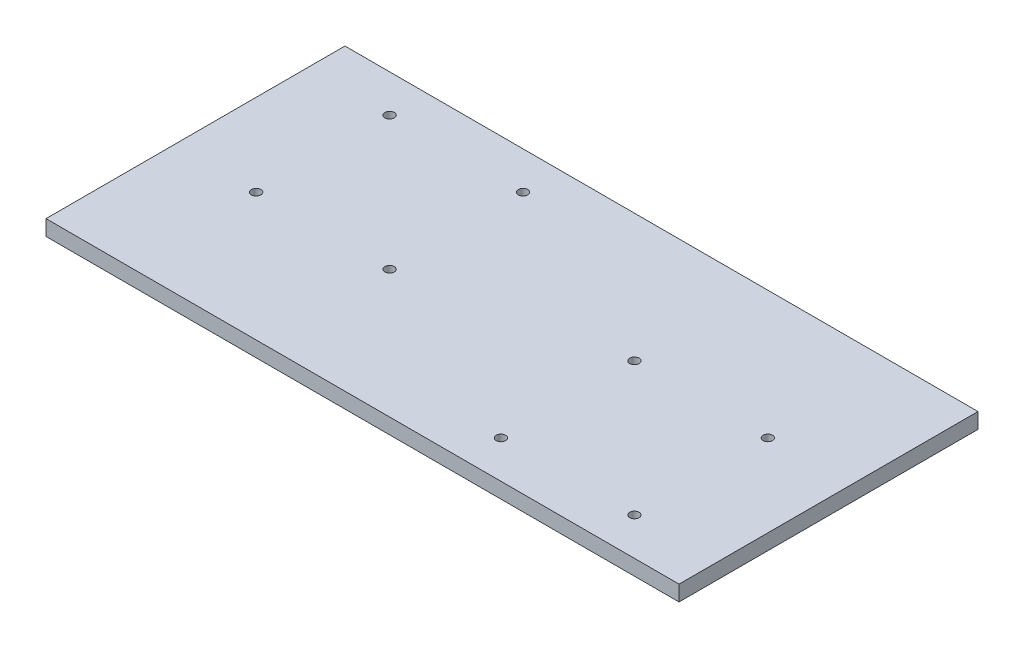
SolidWorks part; units mm, degrees
ref_plane "Front Plane" through (0, 0, 0) normal (0, 0, 1) x (1, 0, 0)
ref_plane "Top Plane" through (0, 0, 0) normal (0, 1, 0) x (1, 0, 0)
ref_plane "Right Plane" through (0, 0, 0) normal (1, 0, 0) x (0, 0, -1)
sketch "Sketch1" plane through (0, 0, 0) normal (0, 1, 0) x (1, 0, 0)
  line L1 (-114.3, -53.975) -> (114.3, -53.975)
  line L2 (-114.3, -53.975) -> (-114.3, 53.975)
  line L3 (-114.3, 53.975) -> (114.3, 53.975)
  line L4 (114.3, -53.975) -> (114.3, 53.975)
  line L5 (-114.3, -53.975) -> (114.3, 53.975) construction
  line L6 (-114.3, 53.975) -> (114.3, -53.975) construction
  point P0 (0, 0)
  dimension "D1" = 107.95
  dimension "D2" = 228.6
extrude "Boss-Extrude1" add sketch "Sketch1" along normal blind 5.588
sketch "Sketch2" plane through (0, 5.588, 0) normal (0, 1, 0) x (1, 0, 0)
  point P0 (-84.612, -7.775)
  point P1 (-84.612, 40.415)
  point P3 (-36.422, 40.415)
  point P5 (-36.422, -7.775)
  point P7 (84.612, -40.415)
  point P9 (84.612, 7.775)
  point P11 (36.422, 7.775)
  point P13 (36.422, -40.415)
hole_wizard "M3 Clearance Hole1" positions "Sketch3" profile "Sketch4" hole size "M3" standard "ANSI Metric" end condition through all
sketch "Sketch3" plane through (0, 5.588, 0) normal (0, 1, 0) x (1, 0, 0)
  point P0 (-84.612, -7.775)
  point P3 (-84.612, 40.415)
  point P6 (-36.422, 40.415)
  point P9 (-36.422, -7.775)
  point P12 (84.612, 7.775)
  point P15 (84.612, -40.415)
  point P18 (36.422, -40.415)
  point P21 (36.422, 7.775)
sketch "Sketch4" plane through (-84.612, 5.588, 7.775) normal (1, 0, 0) x (0, 0, 1)
  line L0 (0, 0) -> (0, 5.588)
  line L1 (0, 5.588) -> (1.7, 5.588)
  line L2 (1.7, 5.588) -> (1.7, 0)
  line L5 (1.7, 0) -> (0, 0)
  line L11 (0, -6.35) -> (0, 107.95) construction
  dimension "Thru Hole Dia." = 3.4
  dimension "Thru Hole Depth" = 5.588
